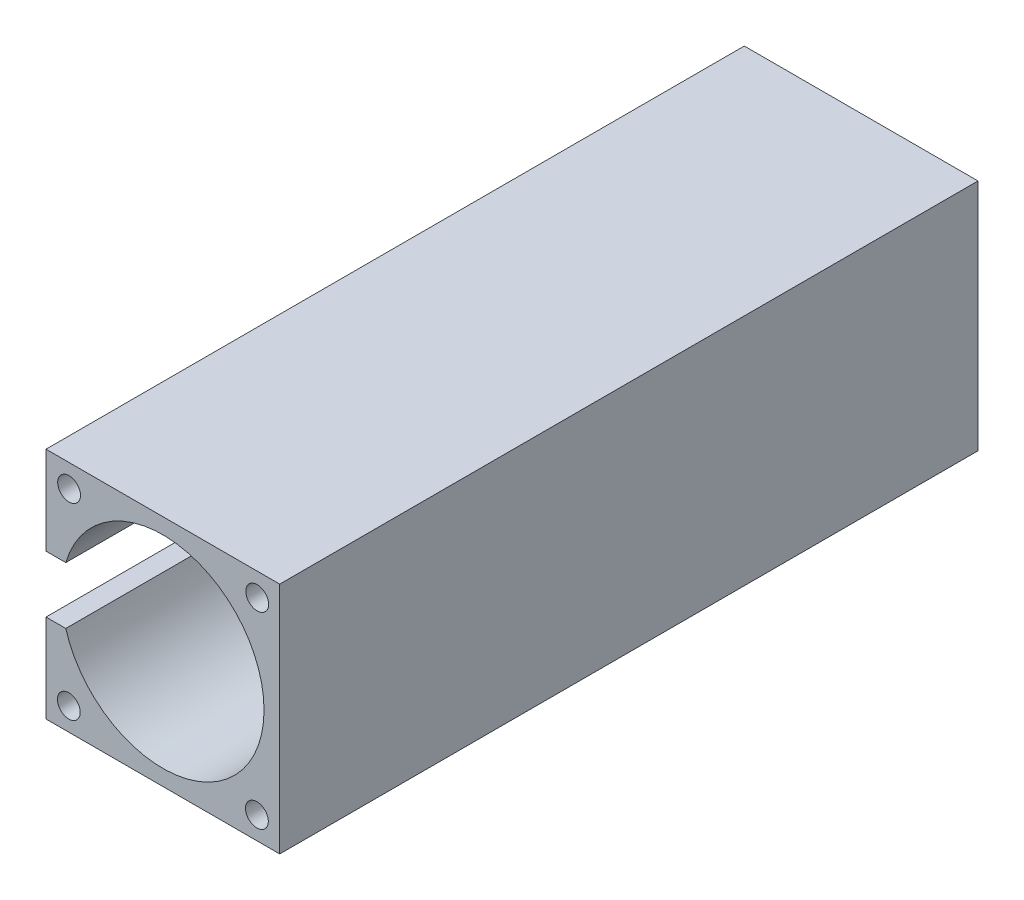
SolidWorks part; units mm, degrees
ref_plane "前基準面" through (0, 0, 0) normal (0, 0, 1) x (1, 0, 0)
ref_plane "上基準面" through (0, 0, 0) normal (0, 1, 0) x (1, 0, 0)
ref_plane "右基準面" through (0, 0, 0) normal (1, 0, 0) x (0, 0, -1)
ref_axis "基準軸1" through (0, -55, 0) along (0, 1, 0)
ref_axis "基準軸2" through (-88.99, 0, 0) along (1, 0, 0)
ref_axis "基準軸3" through (0, 0, 55) along (0, 0, -1)
sketch "草圖1" plane through (0, 0, 0) normal (0, 0, 1) x (1, 0, 0)
  line L0 (0, -55) -> (0, 55) construction
  line L1 (-41, -41) -> (41, -41)
  line L2 (-41, -41) -> (-41, 41)
  line L3 (-41, 41) -> (41, 41)
  line L4 (41, -41) -> (41, 41)
  line L5 (55, 0) -> (-55, 0) construction
  circle A0 centre (0, 0) radius 35.5
  point P7 (0, -41)
  point P10 (41, 0)
  dimension "D1" = 71
  dimension "D2" = 82
  dimension "D3" = 82
extrude "填料-伸長1" add sketch "草圖1" along normal blind 245
sketch "草圖2" plane through (0, 0, 0) normal (0, 0, -1) x (-1, 0, 0)
  line L1 (-41, 41) -> (41, 41)
  line L2 (-41, 41) -> (-41, -41)
  line L3 (-41, -41) -> (41, -41)
  line L4 (41, 41) -> (41, -41)
extrude "填料-伸長2" add sketch "草圖2" along normal blind 27
ref_plane "平面1" through (0, 0, -13.5) normal (0, 0, -1) x (-1, 0, 0)
sketch "草圖3" plane through (0, 0, 245) normal (0, 0, 1) x (1, 0, 0)
  line L0 (-41, 41) -> (-41, -41) construction
  line L1 (-41, 10) -> (-33, 10)
  line L2 (-41, 10) -> (-41, -10)
  line L3 (-41, -10) -> (-33, -10)
  line L4 (-33, 10) -> (-33, -10)
  line L6 (55, 0) -> (-55, 0) construction
  point P6 (-33, 0)
  dimension "D1" = 8
  dimension "D2" = 20
extrude "除料-伸長1" cut sketch "草圖3" against normal up to surface (245 mm away) up to face at (35.5, 0, 0)
sketch "草圖4" plane through (0, 0, 245) normal (0, 0, 1) x (1, 0, 0)
  line L1 (41, 41) -> (-41, 41) construction
  line L2 (-41, 41) -> (-41, 10) construction
  line L3 (-41, -41) -> (41, -41) construction
  line L4 (-41, -10) -> (-41, -41) construction
  circle A0 centre (-32.9, 33) radius 4
  circle A1 centre (33.1, 32.9) radius 4
  circle A2 centre (33, -33.1) radius 4
  circle A3 centre (-33, -33) radius 4
  point P15 (0.05, -0.05)
  dimension "D1" = 8
  dimension "D5" = 8
  dimension "D2" = 8
  dimension "D3" = 8.1
  dimension "D6" = 8
  dimension "D4" = 4
extrude "除料-伸長2" cut sketch "草圖4" against normal blind 20
fillet "圓角2" radius 3 1 edges at (-28.9, 33, 225)
fillet "圓角3" radius 3 1 edges at (37.1, 32.9, 225)
fillet "圓角4" radius 3 1 edges at (-29, -33, 225)
fillet "圓角5" radius 3 1 edges at (37, -33.1, 225)
sketch "草圖5" plane through (0, 41, 0) normal (0, 1, 0) x (1, 0, 0)
  line L0 (-41, -245) -> (-41, 27) construction
  line L4 (-41, 27) -> (41, 27) construction
  circle A2 centre (-36.75, 22.75) radius 1.05
  circle A3 centre (-36.75, 4.75) radius 1.05
  dimension "D1" = 18
  dimension "D2" = 2.1
  dimension "D3" = 2.1
  dimension "D4" = 4.25
  dimension "D5" = 4.25
  dimension "D6" = 4.25
extrude "除料-伸長3" cut sketch "草圖5" against normal blind 10
ref_plane "平面2" through (0, 35, 0) normal (0, 1, 0) x (1, 0, 0)
sketch "草圖6" plane through (0, 35, 0) normal (0, 1, 0) x (1, 0, 0)
  circle A0 centre (-36.75, 22.75) radius 1.05
  circle A1 centre (-36.75, 4.75) radius 1.05
  dimension "D1" = 2.1
  dimension "D2" = 2.1
extrude "填料-伸長3" add sketch "草圖6" along normal blind 0.2
sketch "草圖7" plane through (-41, 0, 0) normal (1, 0, 0) x (0, 0, -1)
  line L1 (27, -41) -> (7, -41)
  line L2 (27, -41) -> (27, 24)
  line L3 (27, 24) -> (7, 24)
  line L4 (7, -41) -> (7, 24)
  dimension "D1" = 20
  dimension "D2" = 65
extrude "除料-伸長5" cut sketch "草圖7" along normal up to next
sketch "草圖8" plane through (0, 41, 0) normal (0, 1, 0) x (1, 0, 0)
  line L0 (0, -45.1) -> (0, 45.1) construction
  line L1 (41, 27) -> (0, 27)
  line L2 (41, 27) -> (41, 7)
  line L3 (41, 7) -> (0, 7)
  line L4 (0, 27) -> (0, 7)
  dimension "D1" = 20
extrude "除料-伸長6" cut sketch "草圖8" against normal up to next
sketch "草圖9" plane through (0, 0, -7) normal (0, 0, -1) x (-1, 0, 0)
  line L0 (-41, -41) -> (-41, 41) construction
  line L1 (-41, -41) -> (41, -41) construction
  line L2 (41, 24) -> (41, -41) construction
  line L3 (0, 41) -> (-41, 41) construction
  line L4 (45.1, 0) -> (-45.1, 0) construction
  circle A0 centre (-33, 33) radius 1.2
  circle A1 centre (-33, -33) radius 1.2
  circle A2 centre (33, -33) radius 1.2
  circle A3 centre (36, 20) radius 1.2
  dimension "D1" = 2.4
  dimension "D2" = 2.4
  dimension "D3" = 2.4
  dimension "D10" = 2.4
  dimension "D4" = 8
  dimension "D5" = 8
  dimension "D6" = 8
  dimension "D7" = 8
  dimension "D8" = 8
  dimension "D9" = 8
  dimension "D11" = 5
  dimension "D12" = 20
extrude "除料-伸長7" cut sketch "草圖9" against normal blind 12
sketch "草圖10" plane through (-41, 0, 0) normal (-1, 0, 0) x (0, 0, 1)
  line L0 (0, -45.1) -> (0, 45.1) construction
  line L1 (0, -41) -> (-27, -41)
  line L2 (0, -41) -> (0, 41)
  line L3 (0, 41) -> (-27, 41)
  line L4 (-27, -41) -> (-27, 41)
  line L5 (0, -55) -> (0, 55) construction
  line L6 (-27, 24) -> (-27, 41) construction
  line L7 (245, 41) -> (-27, 41) construction
  line L8 (245, -41) -> (-7, -41) construction
  dimension "D1" = 0
extrude "除料-伸長8" cut sketch "草圖10" against normal through all both and the other way through all
